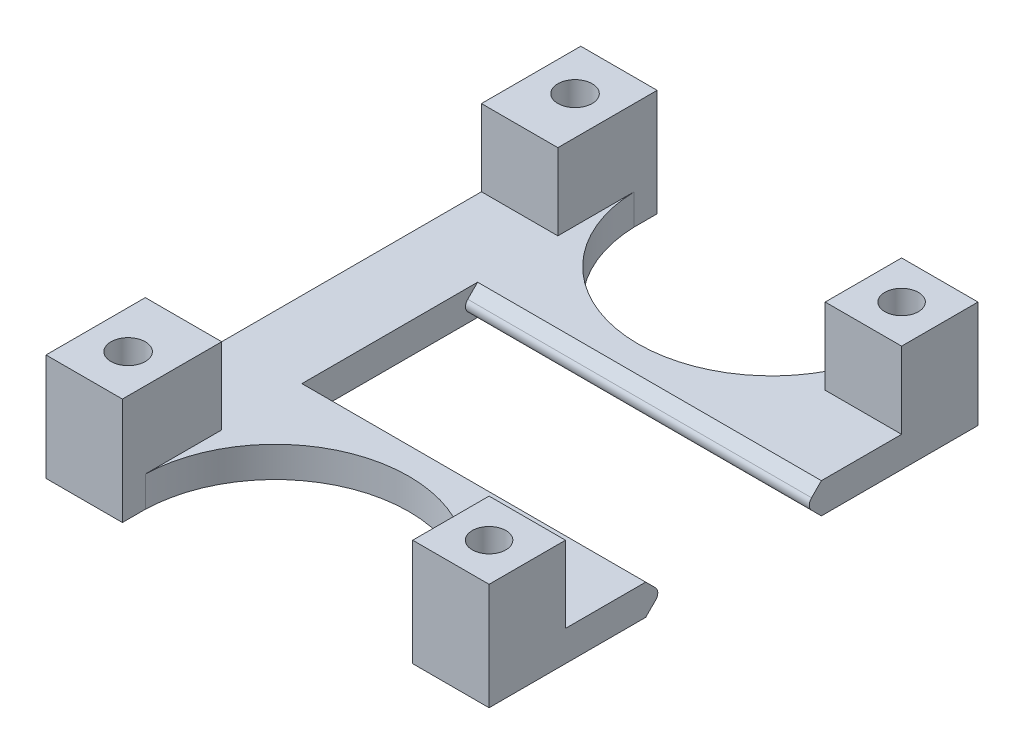
SolidWorks part; units mm, degrees
ref_plane "Front Plane" through (0, 0, 0) normal (0, 0, 1) x (1, 0, 0)
ref_plane "Top Plane" through (0, 0, 0) normal (0, 1, 0) x (1, 0, 0)
ref_plane "Right Plane" through (0, 0, 0) normal (1, 0, 0) x (0, 0, -1)
sketch "Sketch1" plane through (0, 0, 0) normal (0, 1, 0) x (1, 0, 0)
  line L0 (10, 10) -> (10, -10)
  line L2 (0, -20) -> (0, 20)
  line L4 (55, -20) -> (55, 20) construction
  line L5 (10, -10) -> (45, -10)
  line L6 (45, -10) -> (45, 10) construction
  line L7 (45, 10) -> (10, 10)
  line L8 (45, 10) -> (55, 10)
  line L11 (55, 10) -> (55, 20)
  line L13 (27.5, -20) -> (27.5, -10) construction
  line L14 (27.5, 10) -> (27.5, 20) construction
  line L16 (45, -10) -> (55, -10)
  line L17 (55, -20) -> (55, -10)
  line L18 (55, -20) -> (55, -32)
  line L19 (55, -32) -> (45, -32)
  line L20 (0, -32) -> (0, -35)
  line L21 (55, 20) -> (55, 32)
  line L22 (55, 32) -> (45, 32)
  line L23 (0, -35) -> (10, -35)
  line L24 (0, -20) -> (0, -32)
  line L26 (10, -35) -> (10, -32)
  line L27 (0, 20) -> (0, 32)
  line L29 (10, 32) -> (10, 35)
  line L30 (-7.7, 0) -> (7.7, 0) construction
  line L31 (0, 0) -> (55, 0) construction
  line L35 (10, 35) -> (0, 35)
  line L36 (0, 35) -> (0, 32)
  arc A26 (45, -32) -> (10, -32) centre (27.5, -32.5074) ccw
  arc A27 (45, 32) -> (10, 32) centre (27.5, 32.5074) cw
  circle A46 centre (50, 27) radius 2.2
  circle A47 centre (50, -27) radius 2.2
  circle A49 centre (5, 29.25) radius 2.2479 construction
  circle A50 centre (5, 29.25) radius 2.2479
  circle A51 centre (5, -29.25) radius 2.2479 construction
  circle A52 centre (5, -29.25) radius 2.2479
  point P30 (27.5, -15)
  point P35 (27.5, 15)
  point P36 (27.5, -10)
  point P39 (0, 0)
  dimension "D18" = 4.4
  dimension "D1" = 40
  dimension "D2" = 55
  dimension "D24" = 10
  dimension "D13" = 5
  dimension "D16" = 5
  dimension "D7" = 10
  dimension "D9" = 5
  dimension "D14" = 5
  dimension "D4" = 20
  dimension "D5" = 10
  dimension "D3" = 10
  dimension "D6" = 35
  dimension "D8" = 12
  dimension "D10" = 10
extrude "Extrude-Body" add sketch "Sketch1" along normal blind 4 contours L4 L2 A47 A46 L7 L6 L5 L0 | L19 L18 A47 | L22 L21 A46 | L27 | L24 region at (9.1098, 0, 0)
sketch "Sketch5" plane through (0, 4, 0) normal (0, 1, 0) x (1, 0, 0)
  line L9 (45, -22) -> (55, -22)
  line L21 (55, -22) -> (55, -32)
  line L23 (0, -35) -> (0, 35) construction
  line L36 (55, -32) -> (45, -32)
  line L37 (45, -32) -> (45, -22)
  line L38 (55, 22) -> (55, 32)
  line L39 (55, 32) -> (45, 32)
  line L41 (45, 32) -> (45, 22)
  line L42 (45, 22) -> (55, 22)
  line L43 (10, 22) -> (10, 35)
  line L45 (10, 35) -> (0, 35)
  line L46 (0, 35) -> (0, 22)
  line L47 (0, -35) -> (0, 35) construction
  line L48 (0, 22) -> (10, 22)
  line L49 (10, -22) -> (0, -22)
  line L50 (0, -22) -> (0, -35)
  line L52 (10, -35) -> (10, -22)
  line L55 (10, -35) -> (0, -35)
  circle A0 centre (50, 27) radius 2.2
  circle A3 centre (50, -27) radius 2.2
  circle A11 centre (50, 27) radius 2.2 construction
  circle A12 centre (50, -27) radius 2.2 construction
  circle A13 centre (5, -29.25) radius 2.2479 construction
  circle A14 centre (5, -29.25) radius 2.2479
  circle A15 centre (5, 29.25) radius 2.2479 construction
  circle A16 centre (5, 29.25) radius 2.2479
  dimension "D1" = 10
  dimension "D2" = 10
  dimension "D3" = 10
  dimension "D4" = 10
  dimension "D5" = 10
  dimension "D6" = 10
  dimension "D8" = 13
extrude "Extrude-Legs" add sketch "Sketch5" along normal blind 10
sketch "Sketch6" plane through (0, 4, 0) normal (0, 1, 0) x (1, 0, 0)
  line L0 (55, -10) -> (55, -22) construction
  line L1 (10, -10) -> (55, -10)
  line L2 (10, -10) -> (10, -9.5)
  line L3 (10, -9.5) -> (55, -9.5)
  line L4 (55, -10) -> (55, -9.5)
  line L5 (10, 10) -> (55, 10)
  line L6 (10, 10) -> (10, 9.5)
  line L7 (10, 9.5) -> (55, 9.5)
  line L8 (55, 10) -> (55, 9.5)
  line L9 (55, 10) -> (55, 22) construction
  dimension "D1" = 19
extrude "Boss-Extrude1" add sketch "Sketch6" against normal up to surface (4 mm away) up to face at (5, 0, 31.4979)
sketch "Sketch7" plane through (55, 0, 0) normal (1, 0, 0) x (0, 0, -1)
  line L0 (-10.2071, 2.7071) -> (-11.5, 4)
  line L1 (-9.5, 0) -> (-9.5, 4) construction
  line L2 (-9.5, 4) -> (-22, 4) construction
  line L3 (-10.2071, 1.2929) -> (-11.5, 0)
  line L4 (-9.5, 0) -> (-32, 0) construction
  line L5 (10.2071, 2.7071) -> (11.5, 4)
  line L6 (9.5, 0) -> (9.5, 4) construction
  line L7 (9.5, 4) -> (22, 4) construction
  line L8 (10.2071, 1.2929) -> (11.5, 0)
  line L9 (9.5, 0) -> (32, 0) construction
  line L10 (11.5, 4) -> (9.5, 4)
  line L11 (9.5, 0) -> (9.5, 4) construction
  line L12 (9.5, 4) -> (9.5, 0)
  line L13 (9.5, 0) -> (11.5, 0)
  line L14 (-11.5, 4) -> (-9.5, 4)
  line L15 (-9.5, 4) -> (-9.5, 0)
  line L16 (-9.5, 0) -> (-11.5, 0)
  line L17 (0, 0) -> (0, 8.2974) construction
  arc A0 (10.2071, 2.7071) -> (10.2071, 1.2929) centre (10.9142, 2) ccw
  arc A1 (-10.2071, 2.7071) -> (-10.2071, 1.2929) centre (-10.9142, 2) cw
  point P36 (9.5, 2)
  point P39 (-9.5, 2)
  dimension "D3" = 1
  dimension "D1" = 45
  dimension "D2" = 45
extrude "Cut-Extrude1" cut sketch "Sketch7" against normal up to surface (45 mm away) up to face at (10, 2, 0)
equation "\"boltdiameter\"=4.4"
equation "\"D18@Sketch1\"=\"boltdiameter\""
equation "\"boltfacediameter\"=7"
equation "\"insetNutFlat\"=8.4"
equation "\"screwInset\"=8.43"
equation "\"slotLength\"=80"
